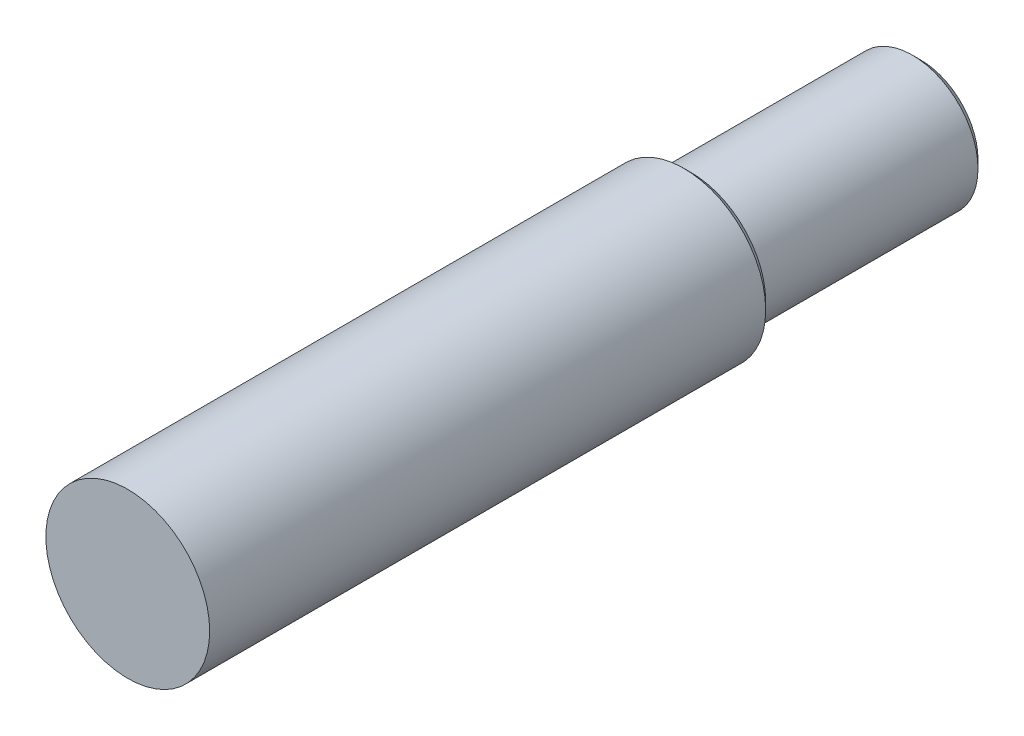
SolidWorks part; units mm, degrees
ref_plane "Front Plane" through (0, 0, 0) normal (0, 0, 1) x (1, 0, 0)
ref_plane "Top Plane" through (0, 0, 0) normal (0, 1, 0) x (1, 0, 0)
ref_plane "Right Plane" through (0, 0, 0) normal (1, 0, 0) x (0, 0, -1)
sketch "Sketch1" plane through (0, 0, 0) normal (1, 0, 0) x (0, 0, -1)
  line L0 (0, 0) -> (0, 5)
  line L1 (0, 5) -> (33.94, 5)
  line L2 (33.94, 5) -> (34.4, 4.54)
  line L3 (34.4, 4.54) -> (34.4, 4)
  line L4 (34.4, 4) -> (47.9, 4)
  line L5 (47.9, 4) -> (48.4, 3.5)
  line L6 (48.4, 3.5) -> (48.4, 0)
  line L7 (48.4, 0) -> (0, 0)
  line L8 (48.4, 0) -> (0, 0) construction
revolve "Revolve1" add sketch "Sketch1" angle 360 about L8 reverse direction yes
cosmetic thread "Cosmetic Thread1" parameters "D1"=10, "D2"=9.08
ref_plane "ANBAU XY" through (0, 0, 0) normal (0, 0, 1) x (1, 0, 0)
ref_plane "ANBAU XZ" through (0, 0, 0) normal (0, -1, 0) x (-1, 0, 0)
ref_plane "ANBAU YZ" through (0, 0, 0) normal (1, 0, 0) x (0, 0, -1)
ref_axis "ANBAU X" through (-80.9, 0, 0) along (1, 0, 0)
ref_axis "ANBAU Y" through (0, -50, 0) along (0, 1, 0)
ref_axis "ANBAU Z" through (0, 0, 80.9) along (0, 0, -1)
sketch3d "ANBAU"
  point P0 (0, 0, 0)
other "Freeze***"
